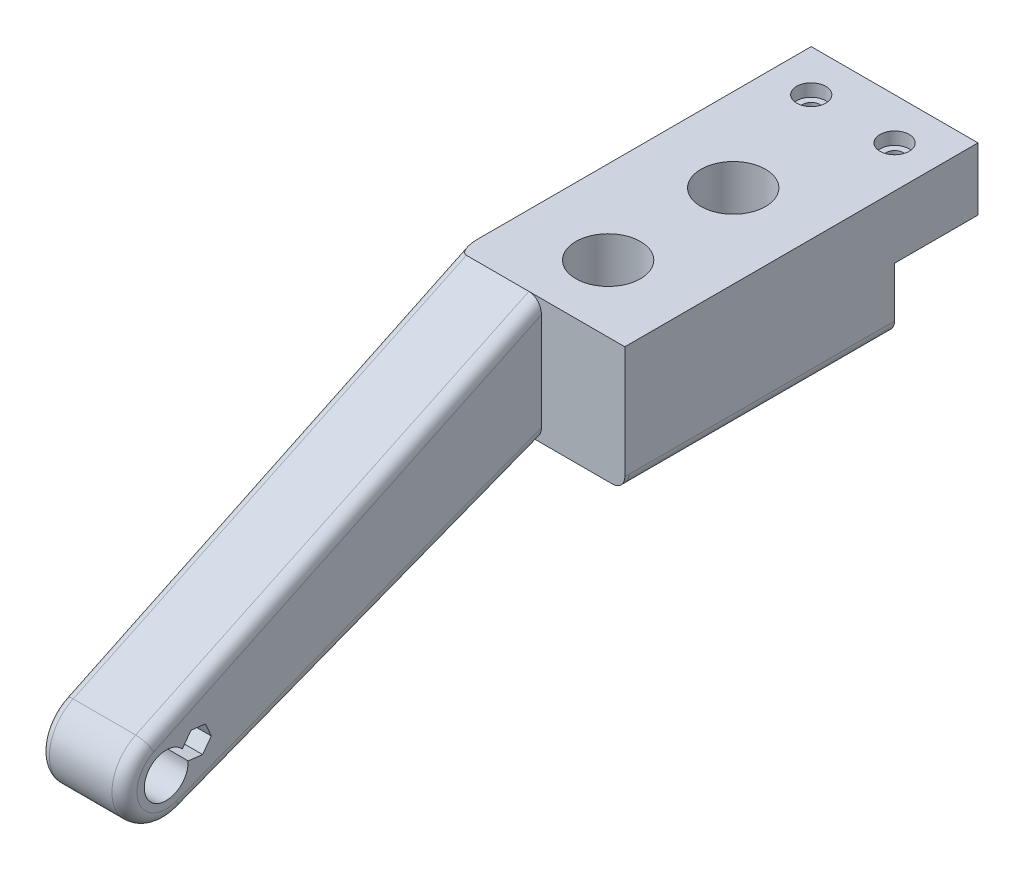
SolidWorks part; units mm, degrees
ref_plane "Front Plane" through (0, 0, 0) normal (0, 0, 1) x (1, 0, 0)
ref_plane "Top Plane" through (0, 0, 0) normal (0, 1, 0) x (1, 0, 0)
ref_plane "Right Plane" through (0, 0, 0) normal (1, 0, 0) x (0, 0, -1)
sketch "Sketch1" plane through (0, 0, 0) normal (0, 1, 0) x (1, 0, 0)
  line L1 (-20, 75) -> (20, 75)
  line L3 (-20, -75) -> (20, -75)
  line L4 (20, -75) -> (20, 75)
  line L5 (-20, -75) -> (-20, 75)
  circle A0 centre (0, -61.1649) radius 7.5
  circle A1 centre (0, -31.1649) radius 7.5
extrude "Boss-Extrude1" add sketch "Sketch1" against normal blind 30 contours L5 L1 L4 L3
sketch "Sketch3" plane through (0, 0, 0) normal (0, 1, 0) x (1, 0, 0)
  circle A0 centre (0, -60) radius 7.5
  circle A1 centre (0, -30) radius 7.5
extrude "Cut-Extrude1" cut sketch "Sketch3" against normal blind 30 contours A0 | A1
sketch "Sketch4" plane through (-20, 0, 0) normal (-1, 0, 0) x (0, 0, 1)
  line L1 (-75, -30) -> (-75, 0) construction
  line L2 (-75, -8) -> (0, -30)
  line L3 (75, -30) -> (-75, -30) construction
  line L4 (0, -30) -> (-75, -30)
  line L5 (-75, -30) -> (-75, -8)
extrude "Cut-Extrude2" cut sketch "Sketch4" against normal blind 49
sketch "Sketch6" plane through (0, 0, -75) normal (0, 0, -1) x (-1, 0, 0)
  line L1 (-20, 0) -> (20, 0)
  line L2 (-20, 0) -> (-20, -30)
  line L3 (-20, -30) -> (20, -30)
  line L4 (20, 0) -> (20, -30)
extrude "Boss-Extrude2" add sketch "Sketch6" along normal blind 50 and the other way blind 87
sketch "Sketch7" plane through (-20, 0, 0) normal (-1, 0, 0) x (0, 0, 1)
  line L1 (-125, -30) -> (-125, 0) construction
  line L2 (-125, -10) -> (-25, -30)
  line L3 (75, -30) -> (-125, -30) construction
  line L4 (-25, -30) -> (-125, -30)
  line L5 (-125, -30) -> (-125, -10)
extrude "Cut-Extrude3" cut sketch "Sketch7" against normal blind 50
sketch "Sketch8" plane through (0, 0, 75) normal (0, 0, 1) x (1, 0, 0)
  line L10 (20, -30) -> (6, -30)
  line L11 (-20, -30) -> (20, -30) construction
  line L12 (6, -30) -> (6, 0)
  line L13 (-20, 0) -> (20, 0) construction
  line L14 (6, 0) -> (20, 0)
  line L15 (20, 0) -> (20, -30)
  line L16 (-20, -30) -> (-6, -30)
  line L17 (-6, -30) -> (-6, 0)
  line L18 (-6, 0) -> (-20, 0)
  line L19 (-20, -30) -> (-20, 0) construction
  line L20 (-20, 0) -> (-20, -30)
extrude "Boss-Extrude4" add sketch "Sketch8" along normal blind 50
sketch "Sketch11" plane through (0, 0, 0) normal (0, 1, 0) x (1, 0, 0)
  line L0 (6, -75) -> (20, -75)
  line L1 (20, -125) -> (20, 125) construction
  line L2 (20, -75) -> (20, -125)
  line L3 (20, -125) -> (6, -125)
  line L4 (6, -125) -> (6, -75)
  line L5 (-6, -75) -> (-6, -125)
  line L6 (-6, -125) -> (-20, -125)
  line L7 (-20, -125) -> (-20, -75)
  line L8 (-20, -125) -> (-20, 125) construction
  line L9 (-20, -75) -> (-6, -75)
extrude "Cut-Extrude4" cut sketch "Sketch11" against normal blind 15
sketch "Sketch12" plane through (0, 0, 125) normal (0, 0, 1) x (1, 0, 0)
  line L1 (-20, -15) -> (-6, -15)
  line L2 (-20, -15) -> (-20, -30)
  line L3 (-20, -30) -> (-6, -30)
  line L4 (-6, -15) -> (-6, -30)
  line L5 (6, -15) -> (20, -15)
  line L6 (6, -15) -> (6, -30)
  line L7 (6, -30) -> (20, -30)
  line L8 (20, -15) -> (20, -30)
extrude "Boss-Extrude5" add sketch "Sketch12" along normal blind 10
sketch "Sketch13" plane through (-6, 0, 0) normal (1, 0, 0) x (0, 0, -1)
  circle A0 centre (-125, -22.5) radius 5
extrude "Boss-Extrude6" add sketch "Sketch13" along normal up to surface (12 mm away) contours A0 up to face at (6, -22.5, 105)
sketch "Sketch14" plane through (0, -30, 0) normal (0, -1, 0) x (1, 0, 0)
  circle A0 centre (0, 60) radius 7.5
  circle A1 centre (0, 60) radius 6
  circle A2 centre (0, 30) radius 6
  circle A3 centre (0, 30) radius 7.5
extrude "Boss-Extrude7" add sketch "Sketch14" against normal blind 5
sketch "Sketch15" plane through (20, 0, 0) normal (1, 0, 0) x (0, 0, -1)
  line L0 (125, 0) -> (105, 0)
  line L1 (-75, 0) -> (125, 0) construction
  circle A0 centre (52.5, 373.9316) radius 377.5991
extrude "Cut-Extrude5" cut sketch "Sketch15" against normal blind 50 contours A0
fillet "Fillet1" radius 3 2 edges at (20, -30, 55) (-20, -30, 55)
fillet "Fillet2" radius 3 8 edges at (-20, -18.5, -82.5) (-19.1213, -29.1213, -29.3934) (0, -30, -25) (19.1213, -29.1213, -29.3934) (-20, -5, -125) (20, -5, -125) (0, -10, -125) (20, -18.5, -82.5)
sketch "Sketch17" plane through (0, 0, 75) normal (0, 0, 1) x (1, 0, 0)
  line L0 (20, 0) -> (20, -30)
  line L1 (14.0365, -30) -> (20, -30)
  line L2 (6, -30) -> (17, -30) construction
  line L3 (20, 0) -> (-20, 0)
  line L4 (-20, 0) -> (-20, -30)
  line L5 (-20, -30) -> (14.0365, -30)
extrude "Boss-Extrude11" add sketch "Sketch17" along normal up to surface (60 mm away) up to face at (13.9243, -23.5243, 135)
sketch "Sketch23" plane through (0, 0, 135) normal (0, 0, 1) x (1, 0, 0)
  line L0 (-20, -15) -> (0, -15)
  line L1 (-20, 0) -> (-20, -30) construction
  line L3 (0, -30) -> (0, -15)
  line L4 (-20, -30) -> (20, -30) construction
  line L6 (-20, -30) -> (0, -30)
  line L7 (-20, -15) -> (-20, -30)
  line L9 (-20, -30) -> (20, -30)
  line L10 (-20, -30) -> (-20, 0)
  line L11 (-20, 0) -> (20, 0)
  line L12 (20, -30) -> (20, 0)
  line M1 (-20, 0) -> (-20, -30)
  line M2 (-20, -30) -> (20, -30)
  line M3 (20, -30) -> (20, 0)
  line M4 (20, 0) -> (-20, 0)
extrude "Cut-Extrude8" cut sketch "Sketch23" against normal up to surface (60 mm away) contours L3 L0 M2 M3 M4 M1 region at (3.3333, -12.5, 135) up to face at (19.2071, -29.2071, 75)
sketch "Sketch25" plane through (0, 0, 75) normal (0, 0, 1) x (1, 0, 0)
  line L0 (-20, -15) -> (-20, 0)
  line L1 (-20, 0) -> (0, 0)
  line L2 (-20, 0) -> (20, 0) construction
  line L3 (0, 0) -> (0, -15)
  line L4 (0, -15) -> (-20, -15)
extrude "Boss-Extrude13" add sketch "Sketch25" along normal up to surface (60 mm away) up to face at (-10, -22.5, 135)
sketch "Sketch26" plane through (0, 0, 0) normal (1, 0, 0) x (0, 0, -1)
  circle A0 centre (-125, -15) radius 5
extrude "Boss-Extrude14" add sketch "Sketch26" along normal up to surface (20 mm away) up to face at (20, -9.3154, -31.9576)
sketch "Sketch27" plane through (0, 0, 75) normal (0, 0, 1) x (1, 0, 0)
  line L1 (20, 0) -> (-20, 0)
  line L2 (20, 0) -> (20, -60)
  line L3 (20, -60) -> (-20, -60)
  line L4 (-20, 0) -> (-20, -60)
extrude "Boss-Extrude15" add sketch "Sketch27" along normal up to surface (60 mm away) up to face at (-10, -15, 135)
sketch "Sketch28" plane through (0, 0, 75) normal (0, 0, -1) x (-1, 0, 0)
  line L0 (20, -27) -> (20, -60) construction
  line L1 (-20, -60) -> (20, -60)
  line L2 (-20, -60) -> (-20, -30)
  line L3 (-20, -30) -> (20, -30)
  line L4 (20, -60) -> (20, -30)
extrude "Cut-Extrude9" cut sketch "Sketch28" against normal blind 1
sketch "Sketch29" plane through (0, 0, 135) normal (0, 0, 1) x (1, 0, 0)
  line L0 (20, 0) -> (-20, 0) construction
  line L1 (20, -60) -> (0, -60)
  line L2 (20, -60) -> (20, 0)
  line L3 (20, 0) -> (0, 0)
  line L4 (0, -60) -> (0, 0)
extrude "Cut-Extrude10" cut sketch "Sketch29" against normal up to surface (59 mm away) up to face at (0, -45, 76)
fillet "Fillet6" radius 3 1 edges at (-20, -30, 75.5)
fillet "Fillet7" radius 3 1 edges at (20, -30, 75.5)
sketch "Sketch30" plane through (0, 0, 135) normal (0, 0, 1) x (1, 0, 0)
  line L0 (-20, 0) -> (-20, -30)
  line L1 (-20, 0) -> (-20, -60) construction
  line L2 (-20, -15) -> (0, -15)
  line L3 (0, 0) -> (0, -60) construction
  line L4 (0, -15) -> (0, 0)
  line L5 (0, 0) -> (-20, 0)
  line M1 (0, -60) -> (0, 0)
  line M2 (0, 0) -> (-20, 0)
  line M3 (-20, 0) -> (-20, -60)
extrude "Cut-Extrude11" cut sketch "Sketch30" against normal up to surface (59 mm away) contours L2 M3 M1 M2 region at (-10, -7.5, 135) up to face at (11.5243, -17.5243, 76)
sketch "Sketch31" plane through (0, 0, 0) normal (1, 0, 0) x (0, 0, -1)
  line L0 (-129.7694, -41.2162) -> (-129.0122, -40.847)
  line L1 (-76, -15) -> (-76, -30)
  line L2 (-76, -30) -> (-118.7075, -57.7744)
  line L3 (-129.6113, -41.0081) -> (-129.7694, -41.2162)
  line L4 (-89.6197, -15) -> (-129.6113, -41.0081)
  line L5 (-76, -30) -> (-76, -60)
  line L6 (-76, -60) -> (-135, -60)
  line L7 (-135, -60) -> (-135, -15)
  line L8 (-135, -15) -> (-76, -15)
  line L9 (-96, -19.1494) -> (-129.6113, -41.0081) construction
  line L10 (-96, -15) -> (-96, -19.1494) construction
  circle A0 centre (-125.0122, -50.0122) radius 10
  line M9 (-76, -15) -> (-135, -15)
  line M10 (-135, -15) -> (-135, -60)
  line M11 (-135, -60) -> (-76, -60)
  line M12 (-76, -60) -> (-76, -30)
  dimension "D1" = 20
extrude "Cut-Extrude13" cut sketch "Sketch31" against normal blind 28 contours A0 M10 M11 | A0 L2 M11 M12 | A0 L3 L4 M9 M10 region at (0, -24.9817, 119.9741) region at (0, -57.7806, 132.7806) region at (0, -50.0084, 91.4032)
sketch "Sketch32" plane through (0, 0, 0) normal (1, 0, 0) x (0, 0, -1)
  line L0 (-76, -30) -> (-76, 0)
  line L1 (-76, 0) -> (-129.7694, -41.2162)
  line L2 (-129.7694, -41.2162) -> (-76, -30)
extrude "Boss-Extrude16" add sketch "Sketch32" against normal up to surface (20 mm away) up to face at (-20, -28.5466, 55.3206)
sketch "Sketch33" plane through (0, 0, 0) normal (1, 0, 0) x (0, 0, -1)
  circle A0 centre (-125.0122, -50.0122) radius 5
extrude "Boss-Extrude17" add sketch "Sketch33" along normal up to surface (20 mm away) contours A0 up to face at (20, -11.526, -18.3379)
sketch "Sketch34" plane through (0, 0, 0) normal (1, 0, 0) x (0, 0, -1)
  line L3 (-115.822, -61.5953) -> (-76, -30)
  line L4 (-133.1492, -37.6664) -> (-76, 0)
  line L5 (-76, 0) -> (-76, -30)
  circle A0 centre (-166, -50.0122) radius 10
  arc A1 (-133.1492, -37.6664) -> (-115.822, -61.5953) centre (-125.0122, -50.0122) ccw
extrude "Cut-Extrude15" cut sketch "Sketch34" against normal blind 23 and the other way blind 23
ref_plane "Plane2" through (0, 0, 0) normal (-1, 0, 0) x (0, -1, 0)
sketch "Sketch37" plane through (0, 0, 0) normal (-1, 0, 0) x (0, -1, 0)
  line L0 (40.8407, 169.9854) -> (0, 76)
  line L1 (0, 76) -> (30, 76)
  line L2 (30, 76) -> (59.1837, 162.0146)
  arc A0 (59.1837, 162.0146) -> (40.8407, 169.9854) centre (50.0122, 166) ccw
extrude "Boss-Extrude18" add sketch "Sketch37" along normal up to surface (20 mm away) up to face at (-20, -11.526, -18.3379)
sketch "Sketch39" plane through (0, -4.0358, 0) normal (1, 0, 0) x (0, 0, -1)
  circle A0 centre (-166, -50.0122) radius 4.5
extrude "Boss-Extrude19" add sketch "Sketch39" along normal up to surface (12 mm away)
ref_plane "Plane3" through (0, 0, 0) normal (1, 0, 0) x (0, 0, -1)
sketch "Sketch40" plane through (0, 0, 0) normal (1, 0, 0) x (0, 0, -1)
  line L0 (-166, -54.048) -> (-166, -54.0122)
  line L1 (-162.3998, -63.3416) -> (-76, -30)
  line L2 (-76, -30) -> (-76, 0)
  line L3 (-170.3055, -44.9865) -> (-76, 0)
  line L4 (-175.987, -54.5224) -> (-180.0505, -45.7105)
  line L5 (-180.0505, -45.7105) -> (-178.0187, -30)
  line L6 (-178.0187, -30) -> (-76, 0)
  circle A0 centre (-166, -54.0122) radius 10
extrude "Cut-Extrude16" cut sketch "Sketch40" against normal blind 20 contours A0 L3 L6 L5 L4 region at (0, -26.9045, 145.2184)
extrude "Boss-Extrude20" add sketch "Sketch40<3>" against normal blind 20 contours A0 L1 L2 L3 | A0 region at (0, -31.8967, 115.5261) region at (0, -62.1629, 171.2905)
sketch "Sketch40<3>" plane through (0, 0, 0) normal (1, 0, 0) x (0, 0, -1) same geometry as "Sketch40"
fillet "Fillet8" radius 2 3 edges at (-20, -22.4933, 123.1528) (-20, -57.968, 175.1843) (-20, -46.6708, 119.1999)
fillet "Fillet9" radius 3 3 edges at (0, -46.6708, 119.1999) (0, -57.968, 175.1843) (0, -22.4933, 123.1528)
sketch "Sketch42" plane through (20, 0, 0) normal (1, 0, 0) x (0, 0, -1)
  line L0 (105, 0) -> (0, 0)
  line L1 (0, 0) -> (0, -5.8264)
  line L2 (0, -5.8264) -> (105, -5.8264)
  line L3 (105, -5.8264) -> (105, 0)
extrude "Boss-Extrude22" add sketch "Sketch42" against normal up to surface (40 mm away) up to face at (-20, -21.0341, 24.0256)
sketch "Sketch43" plane through (-20, 0, 0) normal (-1, 0, 0) x (0, 0, 1)
  line L0 (71.3548, 0) -> (-122, 0) construction
  line L1 (-24.7029, 0) -> (15.2971, 0)
  line L3 (-24.7029, -27) -> (15.2971, -27)
  line L4 (15.2971, 0) -> (15.2971, -27)
  line L5 (-24.7029, -27) -> (75, -27) construction
  line L6 (-18.7029, -6) -> (9.2971, -6)
  line L7 (9.2971, -6) -> (9.2971, -21)
  line L8 (-18.7029, -21) -> (9.2971, -21)
  line L12 (-18.7029, -21) -> (-93.7029, -6)
  line L13 (-18.7029, -6) -> (-93.7029, -6)
  line L15 (-18.7029, -6) -> (-18.7029, -21) construction
  line L16 (-24.7029, 0) -> (-24.7029, -27) construction
  dimension "D1" = 6
extrude "Cut-Extrude17" cut sketch "Sketch43" against normal blind 59 contours L6 L13 L12 L8 L7 region at (-20, -12.0687, -27.0312)
fillet "Fillet10" radius 2 1 edges at (0, -6, -93.7029)
sketch "Sketch45" plane through (0, 0, 9.2971) normal (0, 0, -1) x (-1, 0, 0)
  line L1 (-20, -21) -> (20, -21)
  line L2 (-20, -21) -> (-20, -6)
  line L3 (-20, -6) -> (20, -6)
  line L4 (20, -21) -> (20, -6)
extrude "Boss-Extrude24" add sketch "Sketch45" along normal blind 28
sketch "Sketch46" plane through (20, 0, 0) normal (1, 0, 0) x (0, 0, -1)
  line L0 (18.7029, -6) -> (18.7029, 0)
  line L1 (-76, 0) -> (122, 0) construction
  line L2 (18.7029, 0) -> (-21.2971, 0)
  line L3 (-21.2971, 0) -> (-21.2971, -30)
  line L4 (-21.2971, -30) -> (18.7029, -30)
  line L5 (18.7029, -30) -> (18.7029, -6)
  line L6 (18.7029, 0) -> (8.7029, 0)
  line L7 (8.7029, 0) -> (8.7029, -15)
  line L8 (8.7029, -15) -> (-11.2971, -15)
  line L9 (-11.2971, -15) -> (-11.2971, -30)
  line M6 (18.7029, -21) -> (18.7029, -6)
  line M10 (122, 0) -> (-76, 0)
  line M13 (-75, -27) -> (24.7029, -27)
sketch "Sketch47" plane through (0, 0, 0) normal (0, 1, 0) x (1, 0, 0)
  line L0 (20, 18.7029) -> (-20, 18.7029)
  line L1 (-20, -71.3548) -> (-20, 122) construction
  line L2 (-20, 18.7029) -> (-20, -1.2971)
  line L3 (-20, -1.2971) -> (-10, -1.2971)
  line L4 (-10, -1.2971) -> (10, -1.2971)
  circle A0 centre (10, -1.2971) radius 2
  circle A1 centre (-10, -1.2971) radius 2
extrude "Cut-Extrude18" cut sketch "Sketch46" against normal blind 49 contours L8 L9 L5 L0 L7 M13 M6 M10 | L9 L4 L5 M13 region at (20, -17.0294, -6.6441) region at (20, -28.5, -3.7029)
sketch "Sketch48" plane through (0, 0, -18.7029) normal (0, 0, 1) x (1, 0, 0)
  line L1 (23.5648, -32.8586) -> (-26.7549, -32.8586)
  line L2 (23.5648, -32.8586) -> (23.5648, 14.6986)
  line L3 (23.5648, 14.6986) -> (-26.7549, 14.6986)
  line L4 (-26.7549, -32.8586) -> (-26.7549, 14.6986)
extrude "Cut-Extrude19" cut sketch "Sketch48" against normal blind 139
extrude "Cut-Extrude20" cut sketch "Sketch47" against normal blind 139 contours A0 | L4 A1 L3 | L3 A1 L4 region at (-10, 0, 0.4482) region at (10, 0, -0.6464) region at (-10, 0, 2.1459)
sketch "Sketch49" plane through (0, 0, 0) normal (0, 1, 0) x (1, 0, 0)
  circle A0 centre (10, -1.2971) radius 1.5
  circle A1 centre (10, -1.2971) radius 3.5
  circle A2 centre (-10, -1.2971) radius 1.5
  circle A3 centre (-10, -1.2971) radius 3.5
extrude "Cut-Extrude21" cut sketch "Sketch49" against normal blind 3
sketch "Sketch51" plane through (0, 0, 0) normal (0, 1, 0) x (1, 0, 0)
  circle A0 centre (0, -60) radius 7.75
  circle A1 centre (0, -30) radius 7.75
extrude "Cut-Extrude23" cut sketch "Sketch51" against normal up to surface (25 mm away) up to face at (0, -25, 54)
sketch "Sketch52" plane through (-20, 0, 0) normal (-1, 0, 0) x (0, 0, 1)
  line L0 (169.4444, -46.7917) -> (163.1198, -61.4757)
  line L1 (166.2821, -54.1337) -> (158.6525, -50.8476)
  circle A0 centre (166, -54.0122) radius 5.25
  circle A1 centre (166, -54.0122) radius 8
  circle A2 centre (158.6525, -50.8476) radius 1.45
extrude "Cut-Extrude24" cut sketch "Sketch52" against normal blind 34 contours L0 A0 | L0 A0 L1 | L1 A0 L0 region at (-20, -54.9596, 168.1997) region at (-20, -51.1245, 164.9974) region at (-20, -55.2676, 163.2129)
extrude "Cut-Extrude25" cut sketch "Sketch52<3>" against normal blind 21 contours L1 A2 A1 | A1 A2 L1 | A1 A2 region at (-20, -50.5522, 159.4749) region at (-20, -50.6137, 158.1096) region at (-20, -51.648, 159.0029)
sketch "Sketch52<3>" plane through (-20, 0, 0) normal (-1, 0, 0) x (0, 0, 1) same geometry as "Sketch52"
sketch "Sketch54" plane through (0, 0, 0) normal (1, 0, 0) x (0, 0, -1)
sketch "Sketch55" plane through (0, 0, 0) normal (1, 0, 0) x (0, 0, -1)
  circle A0 centre (-166, -54.0122) radius 6.5
  circle A1 centre (-166, -54.0122) radius 5.25
sketch "Sketch57" plane through (0, 0, 0) normal (1, 0, 0) x (0, 0, -1)
  line L0 (-158.6525, -50.8476) -> (-166, -54.0122)
  line L6 (-162.3263, -52.4299) -> (-163.7108, -49.2154)
  line L7 (-163.7108, -49.2154) -> (-157.8711, -46.7001)
  line L8 (-158.6525, -50.8476) -> (-160.0371, -47.633)
  line L16 (-160.0371, -47.633) -> (-162.1287, -50.4393)
  line L17 (-162.1287, -50.4393) -> (-160.7441, -53.6538)
  line L18 (-160.7441, -53.6538) -> (-157.268, -54.0621)
  line L19 (-157.268, -54.0621) -> (-155.1764, -51.2558)
  line L20 (-155.1764, -51.2558) -> (-156.561, -48.0413)
  line L21 (-156.561, -48.0413) -> (-160.0371, -47.633)
  circle A0 centre (-158.6525, -50.8476) radius 3.0311 construction
  circle M11 centre (-158.6525, -50.8476) radius 1.45
extrude "Cut-Extrude28" cut sketch "Sketch57" against normal blind 5 and the other way blind 8 contours L20 L21 L8 L0 L18 L19 M11 | L17 L18 L0 | L8 L16 L0 M11 | L16 L17 L0 region at (0, -52.3556, 158.3416) region at (0, -50.0268, 160.6815)
